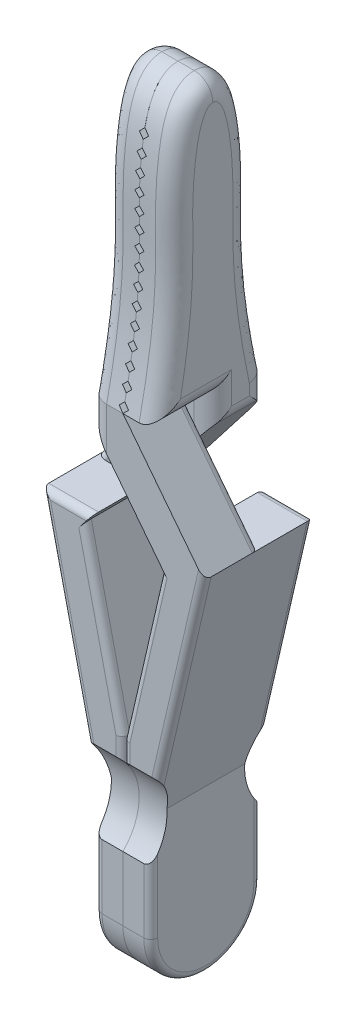
SolidWorks part; units mm, degrees
material "AISI 316 Stainless Steel Sheet (SS)"
ref_plane "Front Plane" through (0, 0, 0) normal (0, 0, 1) x (1, 0, 0)
ref_plane "Top Plane" through (0, 0, 0) normal (0, 1, 0) x (1, 0, 0)
ref_plane "Right Plane" through (0, 0, 0) normal (1, 0, 0) x (0, 0, -1)
sketch "Sketch5" plane through (0, 0, 0) normal (0, 0, 1) x (1, 0, 0)
  line L0 (0, 12.8404) -> (0, 0)
  line L2 (0, 0) -> (3.1622, -4.0657)
  line L3 (3.1622, -4.0657) -> (1.5, -11.2927)
  line L4 (0, 12.8404) -> (1.5, 12.8404)
  line L5 (1.5, 12.8404) -> (1.5, 0.8404)
  line L6 (1.5, 0.8404) -> (5, -3.6596)
  line L7 (5, -3.6596) -> (2.7, -13.6596)
  line L8 (2.7, -13.6596) -> (2.7, -20.6596)
  line L9 (2.7, -20.6596) -> (1.5, -20.6596)
  line L10 (1.5, -20.6596) -> (1.5, -11.2927)
  point P1 (2.7, -3.6316)
  point P2 (2.9485, -0.8433)
  point P13 (0.2356, -10.8513)
  point P14 (0.4202, -13.3189)
  point P15 (2.2681, -3.8682)
  point P16 (0, 0)
  point P17 (4.2674, -3.1992)
  point P18 (4.2047, -2.1172)
  point P19 (0, 0)
  point P20 (0, 0)
  point P21 (3.8993, -1.988)
  point P22 (1.9202, -2.5446)
  point P23 (0, 0)
  point P24 (0, 0)
  point P25 (0, 0)
  point P26 (0.6611, -10.4889)
  point P27 (0, 0)
  point P28 (0, 0)
  point P29 (0, 0.0977)
  point P30 (1.5, -10.9567)
  point P31 (3.0303, -3.6688)
  dimension "D1" = 1.7
  dimension "D2" = 1.5
  dimension "D3" = 12
  dimension "D4" = 10
  dimension "D5" = 7
  dimension "D6" = 1.2
  dimension "D7" = 1.7
  dimension "D8" = 4.5
  dimension "D9" = 5
extrude "Boss-Extrude2" add sketch "Sketch5" along normal blind 4.75
sketch "Sketch6" plane through (0, 0, 0) normal (1, 0, 0) x (0, 0, -1)
  line L0 (0, -3.6596) -> (-2.375, -3.6596)
  line L1 (-2.375, -3.6596) -> (-2.375, 0.8404)
  line L2 (-2.375, 0.8404) -> (0, 0.8404)
  line L3 (-4.75, -3.6596) -> (0, -3.6596) construction
  line L4 (-4.75, 0.8404) -> (0, 0.8404) construction
  line L5 (0, -11.2927) -> (0, -20.6596) construction
  line L6 (0, -15.5113) -> (0, -20.6596) construction
  line L7 (0, 0.8404) -> (0, 12.8404) construction
  line L8 (-2.375, 0.8404) -> (-4.75, 0.8404) construction
  line L9 (-4.75, 0.8404) -> (-4.75, 12.8404) construction
  line L10 (0, -20.6596) -> (-2.375, -20.6596) construction
  line L11 (-4.75, -20.6596) -> (0, -20.6596) construction
  line L12 (0, -18.2846) -> (0, -15.5113)
  line L13 (0, -12.1206) -> (0, -3.6596)
  line L14 (-2.375, 12.8116) -> (-2.375, 7.4216) construction
  line L15 (-4.75, -18.2846) -> (-4.75, -15.5113)
  line L16 (-4.75, 0.8404) -> (-4.75, -12.1206)
  line L17 (-4.75, -11.2927) -> (-4.75, -20.6596) construction
  arc A0 (0, -12.1206) -> (0, -15.5113) centre (1.6954, -13.8159) ccw
  arc A1 (-2.375, -20.6596) -> (0, -18.2846) centre (-2.375, -18.2846) ccw
  arc A2 (-2.375, -20.6596) -> (-4.75, -18.2846) centre (-2.375, -18.2846) cw
  arc A3 (-4.75, -12.1206) -> (-4.75, -15.5113) centre (-6.4454, -13.8159) cw
  spline S0 degree 3 poles (0, 0.8404) (-1.1598, 6.2352) (-0.1869, 8.0351) (-1.2912, 12.7915) (-2.375, 12.8116) knots 0 0 0 0 0.723762 1 1 1 1
  spline S1 degree 3 poles (-4.75, 0.8404) (-3.5902, 6.2352) (-4.5631, 8.0351) (-3.4588, 12.7915) (-2.375, 12.8116) knots 0 0 0 0 0.723762 1 1 1 1
extrude "Cut-Extrude7" cut sketch "Sketch6" along normal through all and the other way through all flip side to cut
ref_plane "Plane2" through (0, 0, 2.375) normal (0, 0, 1) x (1, 0, 0)
fillet "Fillet2" radius 0.8 6 edges at (0, 0.4202, 2.375) (0, 0, 3.5625)
sketch "Sketch8" plane through (0, 0, 2.375) normal (0, 0, 1) x (1, 0, 0)
  line L0 (1.5, 1.2404) -> (1.3, 1.0404)
  line L1 (1.3, 1.0404) -> (1.5, 0.8404)
  line L2 (1.5, 0.8404) -> (1.5, 1.2404)
  line L3 (1.5, 0.8404) -> (1.5, 12.8116) construction
  point P5 (0, 0)
  dimension "D1" = 0.4
extrude "Cut-Extrude8" cut sketch "Sketch8" against normal through all and the other way through all
pattern_linear "LPattern2" count 15 spacing 0.7 along (0, 1, 0) of "Cut-Extrude8"
fillet "Fillet4" radius 0.3 11 edges at (3.25, -1.4096, 2.375) (3.9232, -3.6596, 0) (4.027, -7.8901, 0) (1.5, -11.7066, 4.75) (1.5, -11.7066, 0) (2.3311, -7.6792, 4.75) (2.3311, -7.6792, 0) (2.7, -16.8979, 4.75) (2.7, -16.8979, 0) (4.027, -7.8901, 4.75) (2.7, -20.6596, 2.375)
ref_axis "Axis2" through (1.5, 14.4852, 2.375) along (0, -1, 0)
pattern_circular "CirPattern2" count 2 over 360 about axis through (1.5, 14.4852, 2.375) along (0, -1, 0) of bodies 112
